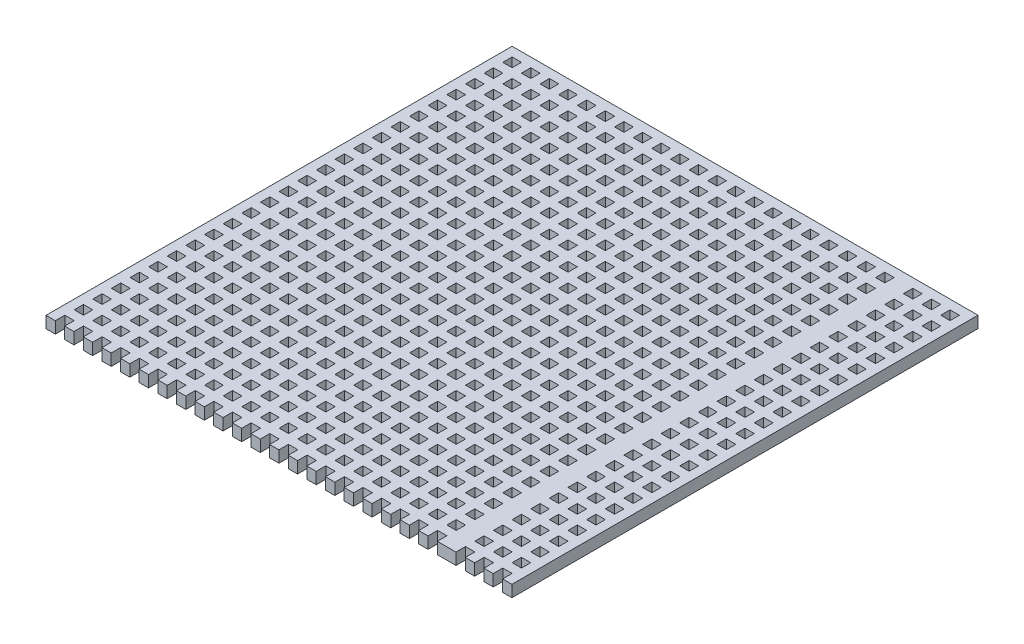
SolidWorks part; units mm, degrees
ref_plane "Front Plane" through (0, 0, 0) normal (0, 0, 1) x (1, 0, 0)
ref_plane "Top Plane" through (0, 0, 0) normal (0, 1, 0) x (1, 0, 0)
ref_plane "Right Plane" through (0, 0, 0) normal (1, 0, 0) x (0, 0, -1)
sketch "Sketch2" plane through (0, 0, 0) normal (0, 1, 0) x (1, 0, 0)
  line L0 (-48, 50) -> (-48, -50)
  line L1 (-50, 50) -> (50, 50)
  line L2 (-50, 50) -> (-50, -50)
  line L3 (-50, -50) -> (50, -50)
  line L4 (50, 50) -> (50, -50)
  line L5 (-50, 50) -> (50, -50) construction
  line L6 (-50, -50) -> (50, 50) construction
  line L7 (-50, 48) -> (50, 48)
  line L8 (50, 48) -> (50, -52)
  line L9 (-50, 46) -> (50, 46)
  line L10 (50, 46) -> (50, -54)
  line L11 (-50, 44) -> (50, 44)
  line L12 (50, 44) -> (50, -56)
  line L13 (-50, 42) -> (50, 42)
  line L14 (50, 42) -> (50, -58)
  line L15 (-50, 40) -> (50, 40)
  line L16 (50, 40) -> (50, -60)
  line L17 (-50, 38) -> (50, 38)
  line L18 (50, 38) -> (50, -62)
  line L19 (-50, 36) -> (50, 36)
  line L20 (50, 36) -> (50, -64)
  line L21 (-50, 34) -> (50, 34)
  line L22 (50, 34) -> (50, -66)
  line L23 (-50, 32) -> (50, 32)
  line L24 (50, 32) -> (50, -68)
  line L25 (-50, 30) -> (50, 30)
  line L26 (50, 30) -> (50, -70)
  line L27 (-50, 28) -> (50, 28)
  line L28 (50, 28) -> (50, -72)
  line L29 (-50, 26) -> (50, 26)
  line L30 (50, 26) -> (50, -74)
  line L31 (-50, 24) -> (50, 24)
  line L32 (50, 24) -> (50, -76)
  line L33 (-50, 22) -> (50, 22)
  line L34 (50, 22) -> (50, -78)
  line L35 (-50, 20) -> (50, 20)
  line L36 (50, 20) -> (50, -80)
  line L37 (-50, 18) -> (50, 18)
  line L38 (50, 18) -> (50, -82)
  line L39 (-50, 16) -> (50, 16)
  line L40 (50, 16) -> (50, -84)
  line L41 (-50, 14) -> (50, 14)
  line L42 (50, 14) -> (50, -86)
  line L43 (-50, 12) -> (50, 12)
  line L44 (50, 12) -> (50, -88)
  line L45 (-50, 10) -> (50, 10)
  line L46 (50, 10) -> (50, -90)
  line L47 (-50, 8) -> (50, 8)
  line L48 (50, 8) -> (50, -92)
  line L49 (-50, 6) -> (50, 6)
  line L50 (50, 6) -> (50, -94)
  line L51 (-50, 4) -> (50, 4)
  line L52 (50, 4) -> (50, -96)
  line L53 (-50, 2) -> (50, 2)
  line L54 (50, 2) -> (50, -98)
  line L55 (-50, 0) -> (50, 0)
  line L56 (50, 0) -> (50, -100)
  line L57 (-50, -2) -> (50, -2)
  line L58 (50, -2) -> (50, -102)
  line L59 (-50, -4) -> (50, -4)
  line L60 (50, -4) -> (50, -104)
  line L61 (-50, -6) -> (50, -6)
  line L62 (50, -6) -> (50, -106)
  line L63 (-50, -8) -> (50, -8)
  line L64 (50, -8) -> (50, -108)
  line L65 (-50, -10) -> (50, -10)
  line L66 (50, -10) -> (50, -110)
  line L67 (-50, -12) -> (50, -12)
  line L68 (50, -12) -> (50, -112)
  line L69 (-50, -14) -> (50, -14)
  line L70 (50, -14) -> (50, -114)
  line L71 (-50, -16) -> (50, -16)
  line L72 (50, -16) -> (50, -116)
  line L73 (-50, -18) -> (50, -18)
  line L74 (50, -18) -> (50, -118)
  line L75 (-50, -20) -> (50, -20)
  line L76 (50, -20) -> (50, -120)
  line L77 (-50, -22) -> (50, -22)
  line L78 (50, -22) -> (50, -122)
  line L79 (-50, -24) -> (50, -24)
  line L80 (50, -24) -> (50, -124)
  line L81 (-50, -26) -> (50, -26)
  line L82 (50, -26) -> (50, -126)
  line L83 (-50, -28) -> (50, -28)
  line L84 (50, -28) -> (50, -128)
  line L85 (-50, -30) -> (50, -30)
  line L86 (50, -30) -> (50, -130)
  line L87 (-50, -32) -> (50, -32)
  line L88 (50, -32) -> (50, -132)
  line L89 (-50, -34) -> (50, -34)
  line L90 (50, -34) -> (50, -134)
  line L91 (-50, -36) -> (50, -36)
  line L92 (50, -36) -> (50, -136)
  line L93 (-50, -38) -> (50, -38)
  line L94 (50, -38) -> (50, -138)
  line L95 (-50, -40) -> (50, -40)
  line L96 (50, -40) -> (50, -140)
  line L97 (-50, -42) -> (50, -42)
  line L98 (50, -42) -> (50, -142)
  line L99 (-50, -44) -> (50, -44)
  line L100 (50, -44) -> (50, -144)
  line L101 (-50, -46) -> (50, -46)
  line L102 (50, -46) -> (50, -146)
  line L103 (-50, -48) -> (50, -48)
  line L104 (50, -48) -> (50, -148)
  line L105 (-50, 50) -> (-50, 48) construction
  point P0 (0, 0)
  dimension "D1" = 100
  dimension "D2" = 100
  dimension "D3" = 2
  dimension "D5" = 2
  dimension "D4" = 50
extrude "Boss-Extrude1" add sketch "Sketch2" along normal blind 2.5 contours L0 L7 L4 L1 | L0 L11 L8 L9 | L0 L15 L12 L13 | L0 L19 L16 L17 | L0 L23 L20 L21 | L0 L27 L24 L25 | L0 L31 L28 L29 | L0 L35 L32 L33 | L0 L39 L36 L37 | L0 L43 L40 L41 | L0 L47 L44 L45 | L0 L51 L48 L49 | L0 L55 L52 L53 | L0 L59 L56 L57 | L0 L63 L60 L61 | L0 L67 L64 L65 | L0 L71 L68 L69 | L0 L75 L72 L73 | L0 L79 L76 L77 | L0 L83 L80 L81 | L0 L87 L84 L85 | L0 L91 L88 L89 | L0 L95 L92 L93 | L0 L99 L96 L97 | L0 L103 L100 L101 | L2 L7 L0 L1 | L2 L11 L0 L9 | L2 L15 L0 L13 | L2 L19 L0 L17 | L2 L23 L0 L21 | L2 L27 L0 L25 | L2 L31 L0 L29 | L2 L35 L0 L33 | L2 L39 L0 L37 | L2 L43 L0 L41 | L2 L47 L0 L45 | L2 L51 L0 L49 | L2 L55 L0 L53 | L2 L59 L0 L57 | L2 L63 L0 L61 | L2 L67 L0 L65 | L2 L71 L0 L69 | L2 L75 L0 L73 | L2 L79 L0 L77 | L2 L83 L0 L81 | L2 L87 L0 L85 | L2 L91 L0 L89 | L2 L95 L0 L93 | L2 L99 L0 L97 | L2 L103 L0 L101
sketch "Sketch3" plane through (0, 2.5, 0) normal (0, 1, 0) x (1, 0, 0)
  line L0 (-48, 50.0495) -> (-48, -50.0495)
  line L1 (-50, 50.0495) -> (50, 50.0495)
  line L2 (-50, 50.0495) -> (-50, -50.0495)
  line L3 (-50, -50.0495) -> (50, -50.0495)
  line L4 (50, 50.0495) -> (50, -50.0495)
  line L5 (-50, 50.0495) -> (50, -50.0495) construction
  line L6 (-50, -50.0495) -> (50, 50.0495) construction
  line L7 (-48, 50.0495) -> (-48, -50.0495)
  line L8 (-46, 50.0495) -> (-46, -50.0495)
  line L9 (-44, 50.0495) -> (-44, -50.0495)
  line L10 (-42, 50.0495) -> (-42, -50.0495)
  line L11 (-40, 50.0495) -> (-40, -50.0495)
  line L12 (-38, 50.0495) -> (-38, -50.0495)
  line L13 (-36, 50.0495) -> (-36, -50.0495)
  line L14 (-34, 50.0495) -> (-34, -50.0495)
  line L15 (-32, 50.0495) -> (-32, -50.0495)
  line L16 (-30, 50.0495) -> (-30, -50.0495)
  line L17 (-28, 50.0495) -> (-28, -50.0495)
  line L18 (-26, 50.0495) -> (-26, -50.0495)
  line L19 (-24, 50.0495) -> (-24, -50.0495)
  line L20 (-22, 50.0495) -> (-22, -50.0495)
  line L21 (-20, 50.0495) -> (-20, -50.0495)
  line L22 (-18, 50.0495) -> (-18, -50.0495)
  line L23 (-16, 50.0495) -> (-16, -50.0495)
  line L24 (-14, 50.0495) -> (-14, -50.0495)
  line L25 (-12, 50.0495) -> (-12, -50.0495)
  line L26 (-10, 50.0495) -> (-10, -50.0495)
  line L27 (-8, 50.0495) -> (-8, -50.0495)
  line L28 (-6, 50.0495) -> (-6, -50.0495)
  line L29 (-4, 50.0495) -> (-4, -50.0495)
  line L30 (-2, 50.0495) -> (-2, -50.0495)
  line L31 (0, 50.0495) -> (0, -50.0495)
  line L32 (2, 50.0495) -> (2, -50.0495)
  line L33 (4, 50.0495) -> (4, -50.0495)
  line L34 (6, 50.0495) -> (6, -50.0495)
  line L35 (8, 50.0495) -> (8, -50.0495)
  line L36 (10, 50.0495) -> (10, -50.0495)
  line L37 (12, 50.0495) -> (12, -50.0495)
  line L38 (14, 50.0495) -> (14, -50.0495)
  line L39 (16, 50.0495) -> (16, -50.0495)
  line L40 (18, 50.0495) -> (18, -50.0495)
  line L41 (20, 50.0495) -> (20, -50.0495)
  line L42 (22, 50.0495) -> (22, -50.0495)
  line L43 (24, 50.0495) -> (24, -50.0495)
  line L44 (26, 50.0495) -> (26, -50.0495)
  line L45 (28, 50.0495) -> (28, -50.0495)
  line L46 (30, 50.0495) -> (30, -50.0495)
  line L47 (32, 50.0495) -> (32, -50.0495)
  line L48 (34, 50.0495) -> (34, -50.0495)
  line L49 (36, 50.0495) -> (36, -50.0495)
  line L50 (38, 50.0495) -> (38, -50.0495)
  line L51 (40, 50.0495) -> (40, -50.0495)
  line L52 (42, 50.0495) -> (42, -50.0495)
  line L53 (44, 50.0495) -> (44, -50.0495)
  line L54 (46, 50.0495) -> (46, -50.0495)
  line L55 (48, 50.0495) -> (48, -50.0495)
  line L56 (-50, 50.0495) -> (-48, 50.0495) construction
  point P0 (0, 0)
  line M8 (-50, 48) -> (50, 48)
  dimension "D1" = 2
  dimension "D3" = 2
  dimension "D2" = 50
extrude "Boss-Extrude2" add sketch "Sketch3" against normal blind 2.5 contours L55 L3 L4 M8 | L54 L53 L3 M8 | L52 L51 L3 M8 | L50 L49 L3 M8 | L49 L48 L3 M8 | L47 L46 L3 M8 | L45 L44 L3 M8 | L43 L42 L3 M8 | L41 L40 L3 M8 | L39 L38 L3 M8 | L37 L36 L3 M8 | L35 L34 L3 M8 | L33 L32 L3 M8 | L31 L30 L3 M8 | L29 L28 L3 M8 | L27 L26 L3 M8 | L25 L24 L3 M8 | L23 L22 L3 M8 | L21 L20 L3 M8 | L19 L18 L3 M8 | L17 L16 L3 M8 | L15 L14 L3 M8 | L13 L12 L3 M8 | L11 L10 L3 M8 | L9 L8 L3 M8 | L2 L3 L0 M8
